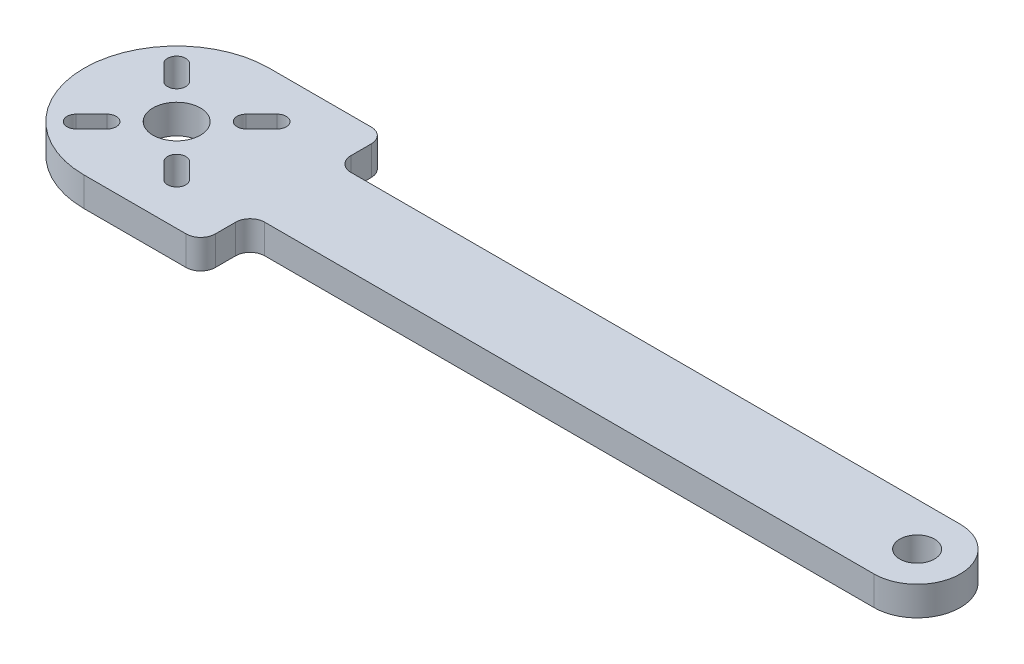
SolidWorks part; units mm, degrees
material "Thornel VCB-20 Carbon Cloth"
ref_plane "Front Plane" through (0, 0, 0) normal (0, 0, 1) x (1, 0, 0)
ref_plane "Top Plane" through (0, 0, 0) normal (0, 1, 0) x (1, 0, 0)
ref_plane "Right Plane" through (0, 0, 0) normal (1, 0, 0) x (0, 0, -1)
sketch "Sketch1" plane through (0, 0, 0) normal (0, 1, 0) x (1, 0, 0)
  line L0 (-58.0134, 7.2134) -> (-43.5866, -7.2134) construction
  line L1 (-50.8, 12.7) -> (-36.8, 12.7)
  line L2 (-50.8, 12.7) -> (-50.8, -12.7) construction
  line L3 (-50.8, -12.7) -> (-36.8, -12.7)
  line L7 (-58.4887, -7.6887) -> (-43.1113, 7.6887) construction
  line L8 (-57.6943, 6.8943) -> (-55.573, 4.773) construction
  line L9 (-56.8104, 7.7782) -> (-54.6891, 5.6569)
  line L10 (-58.5782, 6.0104) -> (-56.4569, 3.8891)
  line L11 (-43.9057, 6.8943) -> (-46.027, 4.773) construction
  line L12 (-43.0218, 6.0104) -> (-45.1431, 3.8891)
  line L13 (-44.7896, 7.7782) -> (-46.9109, 5.6569)
  line L14 (-43.9057, -6.8943) -> (-46.027, -4.773) construction
  line L15 (-44.7896, -7.7782) -> (-46.9109, -5.6569)
  line L16 (-43.0218, -6.0104) -> (-45.1431, -3.8891)
  line L17 (-57.6943, -6.8943) -> (-55.573, -4.773) construction
  line L18 (-58.5782, -6.0104) -> (-56.4569, -3.8891)
  line L19 (-56.8104, -7.7782) -> (-54.6891, -5.6569)
  line L21 (-34.8, 7.9146) -> (-34.8, 10.7)
  line L24 (-34.8, -10.7) -> (-34.8, -7.9146)
  line L32 (-32.8, 5.9146) -> (50.8, 5.9146)
  line L33 (-32.8, -5.9146) -> (50.8, -5.9146)
  line L34 (-50.8, 0) -> (50.8, 0) construction
  arc A0 (-50.8, 12.7) -> (-50.8, -12.7) centre (-50.8, 0) ccw
  circle A2 centre (-50.8, 0) radius 3.25
  arc A3 (-56.8104, 7.7782) -> (-58.5782, 6.0104) centre (-57.6943, 6.8943) ccw
  arc A4 (-56.4569, 3.8891) -> (-54.6891, 5.6569) centre (-55.573, 4.773) ccw
  arc A5 (-43.0218, 6.0104) -> (-44.7896, 7.7782) centre (-43.9057, 6.8943) ccw
  arc A6 (-46.9109, 5.6569) -> (-45.1431, 3.8891) centre (-46.027, 4.773) ccw
  arc A7 (-44.7896, -7.7782) -> (-43.0218, -6.0104) centre (-43.9057, -6.8943) ccw
  arc A8 (-45.1431, -3.8891) -> (-46.9109, -5.6569) centre (-46.027, -4.773) ccw
  arc A9 (-58.5782, -6.0104) -> (-56.8104, -7.7782) centre (-57.6943, -6.8943) ccw
  arc A10 (-54.6891, -5.6569) -> (-56.4569, -3.8891) centre (-55.573, -4.773) ccw
  circle A11 centre (50.8, 0) radius 2.3813
  arc A12 (-34.8, -7.9146) -> (-32.8, -5.9146) centre (-32.8, -7.9146) cw
  arc A13 (-32.8, 5.9146) -> (-34.8, 7.9146) centre (-32.8, 7.9146) cw
  arc A14 (-36.8, -12.7) -> (-34.8, -10.7) centre (-36.8, -10.7) ccw
  arc A15 (-34.8, 10.7) -> (-36.8, 12.7) centre (-36.8, 10.7) ccw
  arc A16 (50.8, 5.9146) -> (50.8, -5.9146) centre (50.8, 0) cw
  point P0 (0, 0)
  point P1 (0, 0)
  point P4 (0, 0)
  point P7 (0, 0)
  point P12 (-50.8, 0)
  point P14 (-50.8, 0)
  point P17 (-56.6336, 5.8336)
  point P27 (-44.9664, 5.8336)
  point P34 (-44.9664, -5.8336)
  point P41 (-56.6336, -5.8336)
  point P46 (-50.8, 0)
  point P53 (-34.8, -5.7)
  point P56 (-34.8, 5.7)
  point P59 (-34.8, -12.7)
  point P62 (-34.8, 12.7)
  point P64 (0, 0)
  dimension "D3" = 6.5
  dimension "D6" = 8.25
  dimension "D10" = 4.7625
  dimension "D17" = 2
  dimension "D18" = 2
  dimension "D16" = 5.9146
  dimension "D2" = 25.4
  dimension "D4" = 45
  dimension "D5" = 45
  dimension "D7" = 3
  dimension "D8" = 2.5
  dimension "D11" = 16
  dimension "D12" = 16
  dimension "D13" = 7
  dimension "D14" = 7
  dimension "D15" = 101.6
  dimension "D19" = 50.8
  dimension "D9" = 4
extrude "Boss-Extrude1" add sketch "Sketch1" along normal blind 4
sketch "Sketch2" plane through (0, 4, 0) normal (0, 1, 0) x (1, 0, 0)
